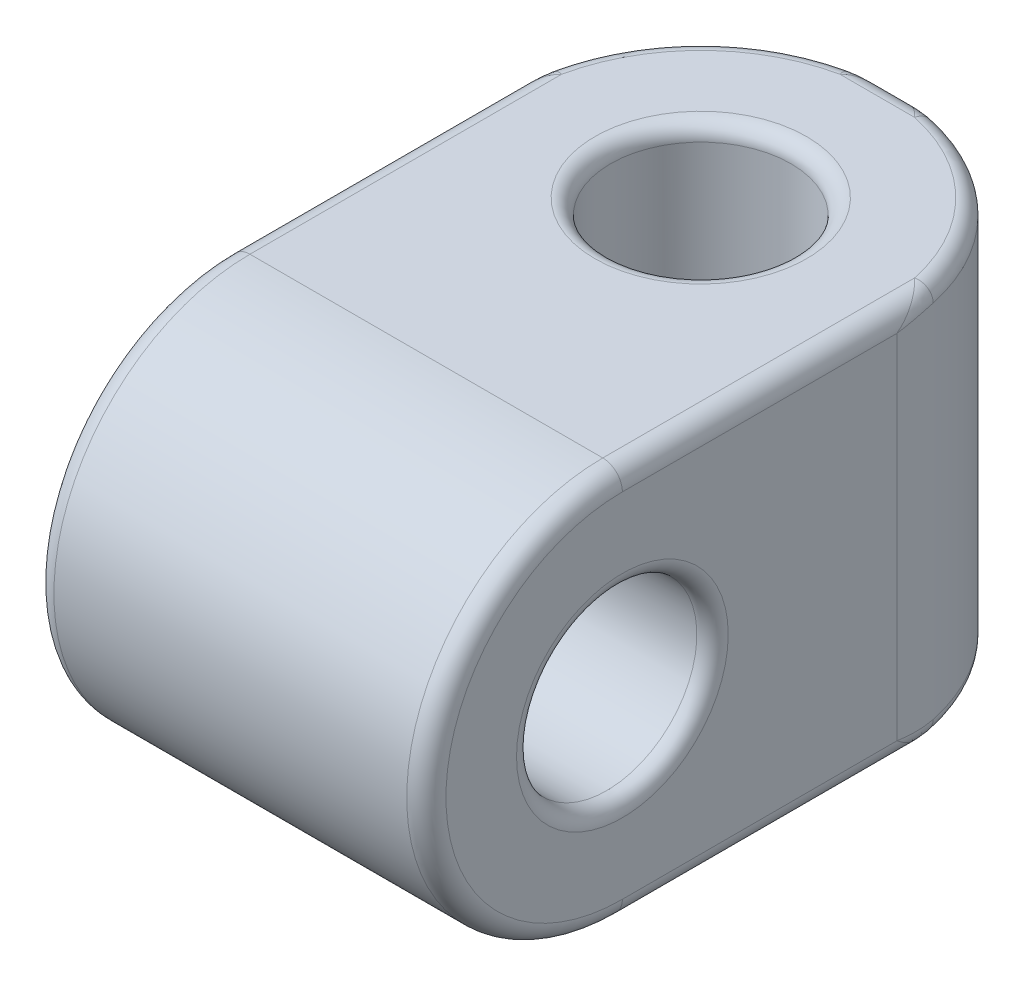
SolidWorks part; units mm, degrees
ref_plane "Front Plane" through (0, 0, 0) normal (0, 0, 1) x (1, 0, 0)
ref_plane "Top Plane" through (0, 0, 0) normal (0, 1, 0) x (1, 0, 0)
ref_plane "Right Plane" through (0, 0, 0) normal (1, 0, 0) x (0, 0, -1)
sketch "Sketch1" plane through (0, 0, 0) normal (1, 0, 0) x (0, 0, -1)
  line L5 (-2, 0) -> (-3, 0)
  line L7 (-2, -2.5) -> (-3, -2.5)
  line L8 (-3, 0) -> (-3, -2.5) construction
  line L9 (-2, 0) -> (0, 0)
  line L11 (-2, -2.5) -> (0, -2.5)
  line L12 (0, 0) -> (0, -2.5) construction
  line L16 (0, -1.25) -> (-3, -1.25) construction
  line L18 (0, 0) -> (0, -2.5)
  circle A0 centre (-3, -1.25) radius 0.575
  arc A1 (-3, -2.5) -> (-3, 0) centre (-3, -1.25) cw
  dimension "D1" = 1.15
  dimension "D2" = 2.5
  dimension "D3" = 3
extrude "Boss-Extrude1" add sketch "Sketch1" along normal blind 2.5
fillet "Fillet1" radius 0.125 8 edges at (0, -2.5, 1.5) (2.5, -2.5, 1.5) (0, -1.25, 4.25) (2.5, -1.25, 4.25) (0, 0, 1.5) (2.5, 0, 1.5) (1.25, -2.5, 0) (1.25, 0, 0)
sketch "Sketch3" plane through (0, 0, 0) normal (0, 1, 0) x (1, 0, 0)
  line L0 (0, -1.25) -> (2.5, -1.25) construction
  line L1 (0, -3) -> (0, 0) construction
  line L2 (2.5, 0) -> (2.5, -3) construction
  line L3 (2.375, 0) -> (0.125, 0) construction
  line L5 (2.5, 0) -> (2.5, -3) construction
  line L6 (0, -1.25) -> (0, 0)
  line L7 (0, 0) -> (0.125, -0.125) construction
  line L8 (0, -3) -> (0, 0) construction
  line L9 (0, 0) -> (2.5, 0)
  line L10 (2.5, 0) -> (2.5, -1.25)
  circle A0 centre (1.25, -1.25) radius 0.575
  arc A1 (0, -1.25) -> (2.5, -1.25) centre (1.25, -1.25) cw
  point P8 (1.25, -1.25)
  line M4 (0.125, -0.125) -> (0.125, -3)
  line M6 (2.375, -3) -> (2.375, -0.125)
  line M9 (2.375, -0.125) -> (0.125, -0.125)
  dimension "D1" = 1.15
  dimension "D2" = 1.25
extrude "Cut-Extrude2" cut sketch "Sketch3" against normal blind 2.5 contours L9 A1 L10 M9 M6 | A1 M9 M6 | L6 A1 L9 M4 M9 | A1 M4 M9 | A0 L0 | L0 A0
fillet "Fillet2" radius 0.1 16 edges at (0, -1.25, 2.425) (2.5, -1.25, 2.425) (1.25, -2.5, 1.825) (1.25, 0, 1.825) (2.4577, -0.0313, 0.9275) (0.3661, 0, 0.3661) (2.1339, 0, 0.3661) (0.502, -0.1443, 0.2485) (1.5725, -0.0313, 0.0423) (0.0423, -0.0313, 0.9275) (0.0423, -2.4687, 0.9275) (0.3661, -2.5, 0.3661) (2.1339, -2.5, 0.3661) (1.5725, -2.4687, 0.0423) (1.004, -2.4493, 0.0244) (2.4577, -2.4687, 0.9275)
